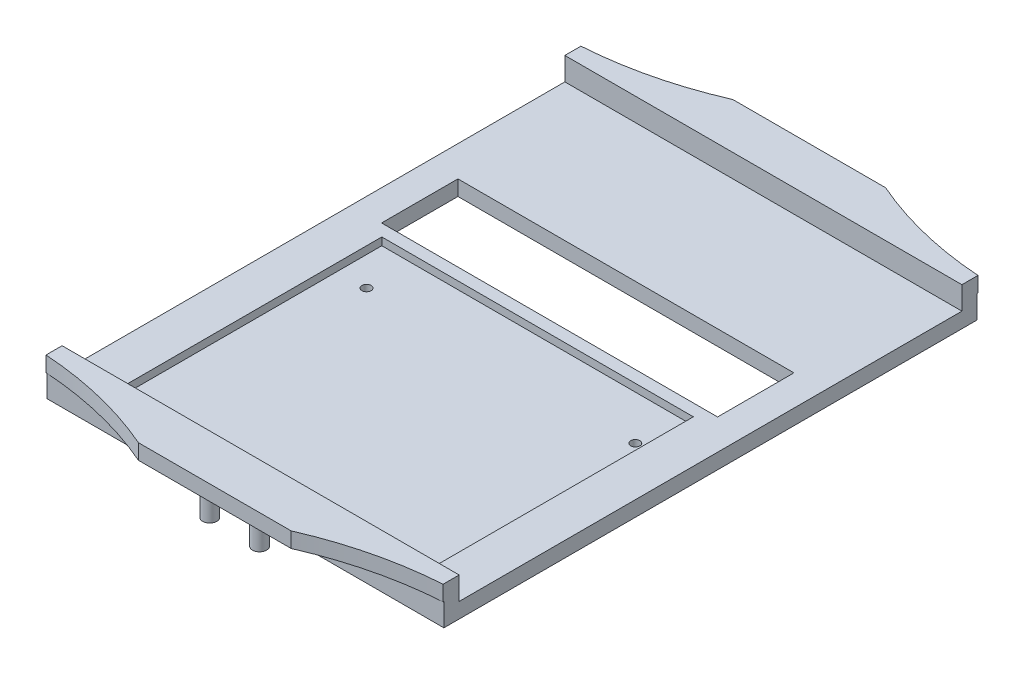
SolidWorks part; units mm, degrees
ref_plane "Front Plane" through (0, 0, 0) normal (0, 0, 1) x (1, 0, 0)
ref_plane "Top Plane" through (0, 0, 0) normal (0, 1, 0) x (1, 0, 0)
ref_plane "Right Plane" through (0, 0, 0) normal (1, 0, 0) x (0, 0, -1)
sketch "Sketch1" plane through (0, 0, 0) normal (1, 0, 0) x (0, 0, -1)
  line L7 (-174.6, 36.382) -> (-174.6, 43.882)
  line L8 (-174.6, 43.882) -> (-184.6, 43.882)
  line L9 (-184.6, 43.882) -> (-184.6, 48.882)
  line L10 (-184.6, 48.882) -> (-169.6, 48.882)
  line L11 (-169.6, 48.882) -> (-169.6, 41.382)
  line L12 (-174.6, 36.382) -> (0, 36.382)
  line L13 (0, 36.382) -> (0, 43.882)
  line L14 (0, 43.882) -> (10, 43.882)
  line L15 (10, 43.882) -> (10, 48.882)
  line L16 (10, 48.882) -> (-5, 48.882)
  line L17 (-5, 48.882) -> (-5, 41.382)
  line L18 (-5, 41.382) -> (-169.6, 41.382)
  dimension "D1" = 194.6
  dimension "D2" = 5
  dimension "D3" = 10
  dimension "D4" = 5
  dimension "D5" = 164.6
  dimension "D6" = 174.6
  dimension "D7" = 2.5
  dimension "D8" = 5
extrude "Boss-Extrude1" add sketch "Sketch1" along normal blind 150
sketch "Sketch2" plane through (0, 0, 0) normal (0, 1, 0) x (1, 0, 0)
  line L2 (50, 10) -> (0, 10)
  line L3 (150, 10) -> (0, 10) construction
  line L9 (100, 10) -> (150, 10)
  line L11 (0, -184.6) -> (50, -184.6)
  line L12 (150, -184.6) -> (0, -184.6) construction
  line L17 (150, -184.6) -> (100, -184.6)
  line L21 (0, 10) -> (0, 0)
  line L22 (0, 0) -> (50, 0)
  line L23 (50, 0) -> (50, 10)
  line L24 (100, 10) -> (100, 0)
  line L25 (100, 0) -> (150, 0)
  line L26 (150, 0) -> (150, 10)
  line L27 (0, -184.6) -> (0, -174.6)
  line L28 (0, -174.6) -> (50, -174.6)
  line L29 (50, -174.6) -> (50, -184.6)
  line L30 (100, -184.6) -> (100, -174.6)
  line L31 (100, -174.6) -> (150, -174.6)
  line L32 (150, -174.6) -> (150, -184.6)
  dimension "D1" = 50
extrude "Cut-Extrude2" cut sketch "Sketch2" along normal up to next
fillet "Fillet1" radius 120 4 edges at (50, 46.382, 174.6) (100, 46.382, 174.6) (100, 46.382, 0) (50, 46.382, 0)
sketch "Sketch4" plane through (0, 48.882, 0) normal (0, 1, 0) x (1, 0, 0)
  line L2 (100, -184.6) -> (50, -184.6) construction
  line L3 (100, 10) -> (50, 10) construction
  circle A0 centre (66.85, -178.1) radius 2.3
  circle A2 centre (83.15, -178.1) radius 2.3
  circle A3 centre (83.15, 3.5) radius 2.3
  circle A4 centre (66.85, 3.5) radius 2.3
  dimension "D2" = 4.6
  dimension "D1" = 16.3
  dimension "D3" = 16.85
  dimension "D4" = 6.5
  dimension "D7" = 6.5
  dimension "D5" = 2
  dimension "D6" = 2
extrude "Boss-Extrude2" add sketch "Sketch4" against normal blind 16
sketch "Sketch7" plane through (0, 32.882, 0) normal (0, -1, 0) x (1, 0, 0)
  circle A0 centre (66.85, 178.1) radius 2.15
  circle A1 centre (83.15, 178.1) radius 2.15
  circle A2 centre (66.85, -3.5) radius 2.15
  circle A3 centre (83.15, -3.5) radius 2.15
  dimension "D1" = 4.3
  dimension "D2" = 4.3
  dimension "D3" = 4.3
  dimension "D4" = 4.3
extrude "Cut-Extrude4" cut sketch "Sketch7" against normal up to surface (11 mm away) up to face at (83.15, 43.882, 180.4)
sketch "Sketch8" plane through (0, 41.382, 0) normal (0, 1, 0) x (1, 0, 0)
  line L0 (20, -75) -> (130, -75)
  line L1 (20, -75) -> (20, -50)
  line L2 (150, -5) -> (0, -5) construction
  line L3 (20, -50) -> (130, -50)
  line L8 (0, -5) -> (0, -169.6) construction
  line L9 (130, -50) -> (130, -75)
  dimension "D1" = 25
  dimension "D2" = 110
  dimension "D3" = 45
  dimension "D4" = 20
extrude "Cut-Extrude5" cut sketch "Sketch8" against normal up to surface (5 mm away) up to face at (75, 36.382, 87.3)
sketch "Sketch10" plane through (0, 41.382, 0) normal (0, 1, 0) x (1, 0, 0)
  line L3 (20, -75) -> (130, -75) construction
  line L12 (25, -78.925) -> (126, -78.925)
  line L13 (126, -78.925) -> (126, -165.6744)
  line L14 (126, -165.6744) -> (24, -165.6744)
  line L15 (24, -165.6744) -> (24, -78.925)
  line L16 (24, -78.925) -> (25, -78.925)
  circle A0 centre (33.5, -93.425) radius 1.5
  circle A1 centre (121.5, -93.425) radius 1.5
  circle A2 centre (121.5, -161.1744) radius 1.5
  circle A3 centre (33.5, -161.1744) radius 1.5
  dimension "D1" = 3
  dimension "D2" = 4.5
  dimension "D3" = 9.5
  dimension "D4" = 4.5
  dimension "D5" = 4.5
  dimension "D7" = 14.5
  dimension "D8" = 14.5
  dimension "D9" = 9.5
  dimension "D10" = 3.925
  dimension "D6" = 4.5
extrude "Cut-Extrude6" cut sketch "Sketch10" against normal blind 2.5 contours L12 L13 L14 L15 L16
extrude "Cut-Extrude7" cut sketch "Sketch10<3>" against normal through all contours A1 | A0 | A3 | A2
sketch "Sketch10<3>" plane through (0, 41.382, 0) normal (0, 1, 0) x (1, 0, 0) same geometry as "Sketch10"
fillet "Fillet2" radius 1 4 edges at (83.15, 43.882, -1.2) (66.85, 43.882, -1.2) (83.15, 43.882, 180.4) (66.85, 43.882, 180.4)
sketch "Sketch11" plane through (0, 41.382, 0) normal (0, 1, 0) x (1, 0, 0)
  line L0 (10, 10) -> (0, 10)
  line L1 (10, -184.6) -> (0, -184.6)
  line L2 (0, 10) -> (0, -184.6)
  line L3 (140, 10) -> (150, 10)
  line L4 (10, 10) -> (10, -184.6)
  line L6 (150, 10) -> (150, -184.6)
  line L8 (140, 10) -> (140, -184.6)
  line L9 (140, -184.6) -> (150, -184.6)
extrude "Cut-Extrude8" cut sketch "Sketch11" along normal through all both and the other way through all
